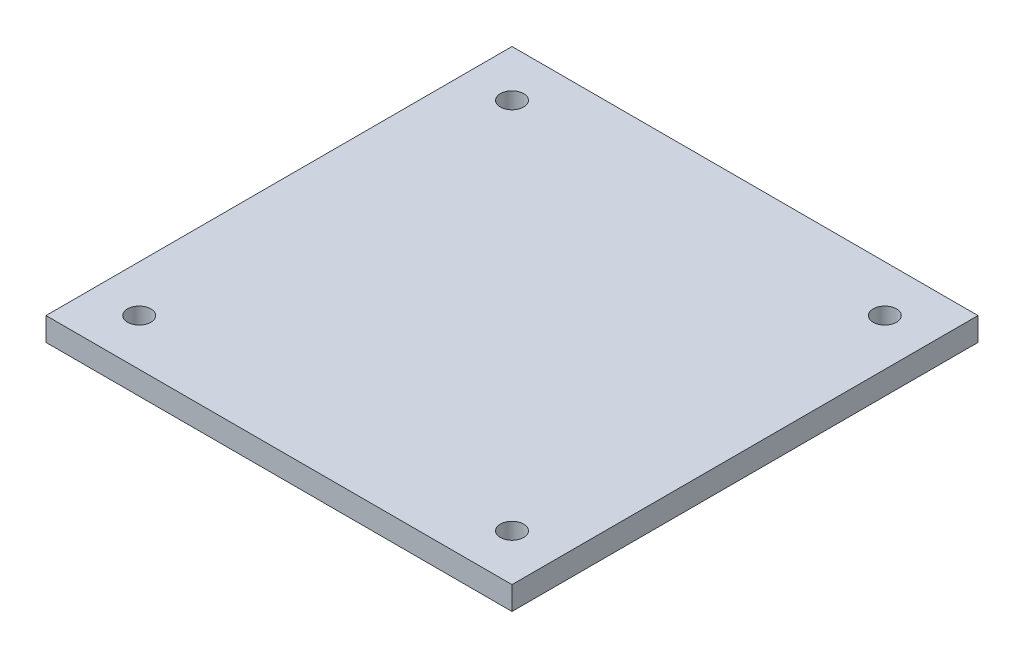
SolidWorks part; units mm, degrees
note: '?' marks a value the reader was unsure of.
other "Connection Feature" parameters "D1"=154.1129
ref_plane "Plane1" through (0, 5, 0) normal (1, 0, 0) x (0, 0, -1)
ref_axis "Axis1" through (0, 5, 50) along (0, 0, -1)?
ref_point "3DPoint1"
ref_plane "Front Plane" through (0, 0, 0) normal (0, 0, 1) x (1, 0, 0)
ref_plane "Top Plane" through (0, 0, 0) normal (0, 1, 0) x (1, 0, 0)
ref_plane "Right Plane" through (0, 0, 0) normal (1, 0, 0) x (0, 0, -1)
sketch "Sketch1" plane through (0, 0, 0) normal (0, 1, 0) x (1, 0, 0)
  line L1 (-50, 50) -> (50, 50)
  line L2 (-50, 50) -> (-50, -50)
  line L3 (-50, -50) -> (50, -50)
  line L4 (50, 50) -> (50, -50)
  line L5 (-50, 50) -> (50, -50) construction
  line L6 (-50, -50) -> (50, 50) construction
  point P0 (0, 0)
  dimension "D1" = 100
extrude "Boss-Extrude1" add sketch "Sketch1" along normal blind 5
hole_wizard "Ø5.0mm Dowel Hole1" positions "Sketch3" profile "Sketch4" hole size "Ø5.0" standard "ANSI Metric" end condition through all
sketch "Sketch3" plane through (0, 5, 0) normal (0, 1, 0) x (1, 0, 0)
  line L0 (50, -50) -> (50, 50) construction
  line L1 (-50, -50) -> (50, -50) construction
  point P0 (40, -40)
  dimension "D1" = 10
  dimension "D2" = 10
sketch "Sketch4" plane through (40, 5, 40) normal (1, 0, 0) x (0, 0, 1)
  line L0 (0, 0) -> (0, 5)
  line L1 (0, 5) -> (2.525, 5)
  line L2 (2.5, 4.975) -> (2.5, 0)
  line L5 (2.5, 0) -> (0, 0)
  line L7 (2.525, 5) -> (2.5, 4.975)
  line L8 (-2.525, 5) -> (-2.5, 4.975) construction
  line L11 (0, -6.35) -> (0, 107.95) construction
  dimension "Thru Hole Dia." = 5
  dimension "Thru Hole Depth" = 5
  dimension "Far C'Sink Dia." = 5.05
  dimension "Far C'Sink Angle" = 90
mirror "Mirror1" about plane through (0, 0, 0) normal (1, 0, 0) of "Ø5.0mm Dowel Hole1" second plane through (0, 0, 0) second plane normal (0, 0, 1)
other "Configuration Table"
